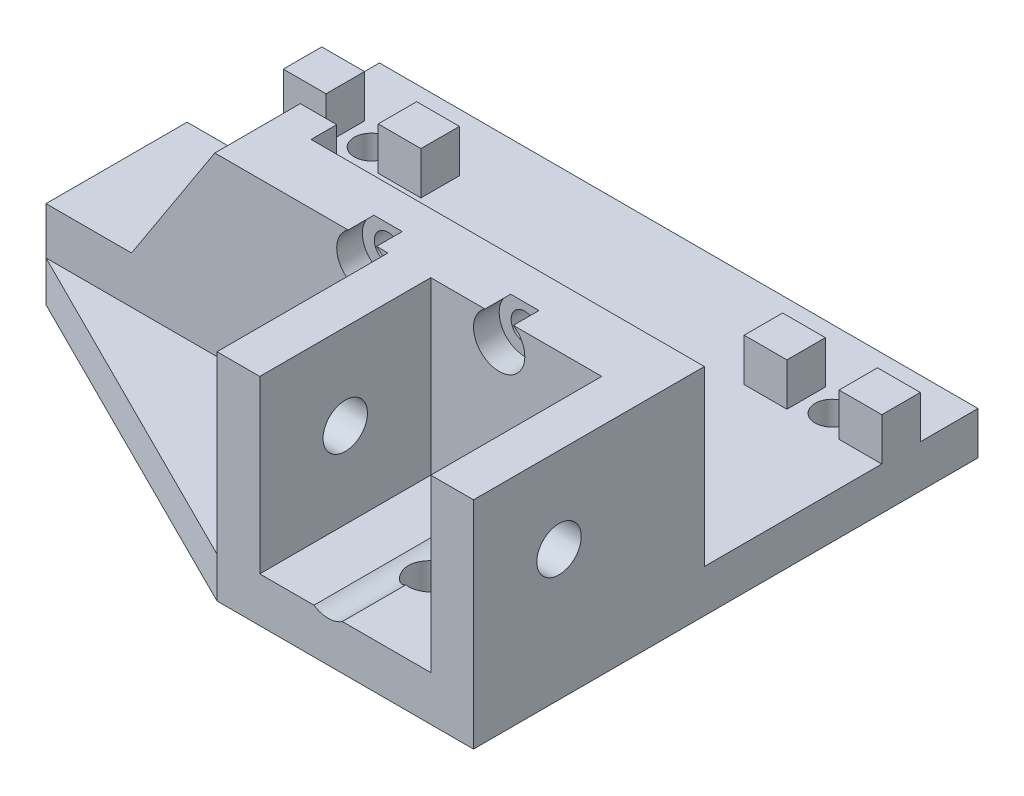
SolidWorks part; units mm, degrees
ref_plane "Front" through (0, 0, 0) normal (0, 0, 1) x (1, 0, 0)
ref_plane "Top" through (0, 0, 0) normal (0, 1, 0) x (1, 0, 0)
ref_plane "Right" through (0, 0, 0) normal (1, 0, 0) x (0, 0, -1)
other "Configuration Table"
sketch "Sketch1" plane through (0, 0, 0) normal (0, 0, 1) x (1, 0, 0)
  line L1 (-20, -10) -> (20, -10)
  line L2 (-20, -10) -> (-20, 10)
  line L3 (-20, 10) -> (20, 10)
  line L4 (20, -10) -> (20, 10)
  line L5 (-20, -10) -> (20, 10) construction
  line L6 (-20, 10) -> (20, -10) construction
  line L7 (-8, -7.5) -> (8, -7.5) construction
  line L8 (-8, -7.5) -> (-8, 7.5) construction
  line L9 (-8, 7.5) -> (8, 7.5) construction
  line L10 (8, -7.5) -> (8, 7.5) construction
  line L11 (-8, -7.5) -> (8, 7.5) construction
  line L12 (-8, 7.5) -> (8, -7.5) construction
  circle A0 centre (-8, 7.5) radius 1.6
  circle A1 centre (8, 7.5) radius 1.6
  circle A2 centre (8, -7.5) radius 1.6
  circle A3 centre (-8, -7.5) radius 1.6
  point P0 (0, 0)
  point P6 (0, 0)
extrude "Boss-Extrude1" add sketch "Sketch1" along normal blind 7
sketch "Sketch2" plane through (20, 0, 0) normal (1, 0, 0) x (0, 0, -1)
  line L0 (0, 0) -> (0, 5) construction
  line L1 (0, -10) -> (0, 10) construction
  line L2 (0, 0) -> (0, -5) construction
  line L3 (0, -5) -> (3, -5) construction
  line L4 (3, -5) -> (3, 5)
  line L5 (3, 5) -> (0, 5) construction
  line L6 (0, -10) -> (9.5, -10)
  line L7 (0, 10) -> (9.5, 10)
  line L8 (9.5, 10) -> (9.5, 5)
  line L9 (9.5, 5) -> (3, 5)
  line L10 (9.5, -10) -> (9.5, -5)
  line L11 (9.5, -5) -> (3, -5)
  line L12 (0, -10) -> (0, -5) construction
  line L13 (0, 5) -> (0, 10) construction
  line L14 (0, -10) -> (-7, -10)
  line L15 (-7, -10) -> (-7, 10)
  line L16 (-7, 10) -> (0, 10)
extrude "Boss-Extrude2" add sketch "Sketch2" along normal blind 5
sketch "Sketch3" plane through (-20, 0, 0) normal (-1, 0, 0) x (0, 0, 1)
  line L0 (7, 10) -> (-9.5, 10)
  line L1 (-9.5, 10) -> (-9.5, 5)
  line L2 (-9.5, 5) -> (-3, 5)
  line L3 (-3, 5) -> (-3, -5)
  line L4 (-3, -5) -> (-9.5, -5)
  line L5 (-9.5, -5) -> (-9.5, -10)
  line L6 (-9.5, -10) -> (7, -10)
  line L7 (7, -10) -> (7, 10)
extrude "Boss-Extrude3" add sketch "Sketch3" along normal blind 5
sketch "Sketch4" plane through (0, -10, 0) normal (0, -1, 0) x (1, 0, 0)
  line L0 (-25, 7) -> (-25, -9.5)
  line L1 (-25, -9.5) -> (-20, -9.5)
  line L2 (-20, -9.5) -> (-20, 0)
  line L3 (-20, 0) -> (20, 0)
  line L4 (20, 0) -> (20, -9.5)
  line L5 (20, -9.5) -> (25, -9.5)
  line L6 (25, -9.5) -> (25, 7)
  line L7 (25, 7) -> (-25, 7)
extrude "Boss-Extrude4" add sketch "Sketch4" along normal blind 0.25
sketch "Sketch5" plane through (0, -10.25, 0) normal (0, -1, 0) x (1, 0, 0)
  line L0 (-20, 0) -> (-20, -29) construction
  line L1 (-25, 7) -> (-25, -29)
  line L2 (25, 7) -> (25, -29)
  line L3 (25, -29) -> (-25, -29)
  line L4 (-25, 7) -> (25, 7)
extrude "Boss-Extrude5" add sketch "Sketch5" along normal blind 5
sketch "Sketch6" plane through (0, 0, 7) normal (0, 0, 1) x (1, 0, 0)
  circle A0 centre (-8, 7.5) radius 3
  circle A1 centre (-8, -7.5) radius 3
  circle A2 centre (8, -7.5) radius 3
  circle A3 centre (8, 7.5) radius 3
extrude "Cut-Extrude1" cut sketch "Sketch6" against normal blind 3
sketch "Sketch7" plane through (-25, 0, 0) normal (-1, 0, 0) x (0, 0, 1)
  line L0 (-3, -5) -> (7, -5)
  line L1 (7, -15.25) -> (7, 10) construction
  line L2 (7, -5) -> (7, -15.25)
  line L3 (7, -15.25) -> (-29, -15.25)
  line L4 (-29, -15.25) -> (-29, -10.25)
  line L5 (-29, -10.25) -> (-9.5, -10.25)
  line L6 (-9.5, -10.25) -> (-9.5, -5)
  line L7 (-9.5, -5) -> (-3, -5)
extrude "Boss-Extrude6" add sketch "Sketch7" along normal blind 20
sketch "Sketch9" plane through (0, 0, 7) normal (0, 0, 1) x (1, 0, 0)
  line L0 (0, 0) -> (20, 0) construction
  line L1 (0, 0) -> (0, 10)
  line L2 (-20, 0) -> (-20, 10) construction
  line L3 (20, 0) -> (20, 10)
  line L4 (-20, 0) -> (-20, -10) construction
  line L5 (20, 0) -> (20, -10)
  line L6 (20, -10) -> (25, -10)
  line L7 (25, 10) -> (25, -15.25) construction
  line L8 (25, -10) -> (25, 10)
  line L9 (25, 10) -> (20, 10)
  line L10 (-20, 10) -> (-25, 10) construction
  line L11 (-25, 10) -> (-25, -10) construction
  line L12 (-25, -10) -> (-20, -10) construction
  line L13 (0, 0) -> (0, -10)
  line L14 (0, 10) -> (-5, 10)
  line L15 (-5, 10) -> (-5, -10)
  line L16 (-5, -10) -> (0, -10)
extrude "Boss-Extrude8" add sketch "Sketch9" along normal blind 20
sketch "Sketch10" plane through (-25, 0, 0) normal (-1, 0, 0) x (0, 0, 1)
  line L0 (0, 0) -> (7, 0) construction
  line L1 (7, 0) -> (7, -5) construction
  line L2 (7, 0) -> (17, 0) construction
  circle A0 centre (17, 0) radius 2.6
extrude "Cut-Extrude2" cut sketch "Sketch10" against normal through all
sketch "Sketch11" plane through (0, 0, 7) normal (0, 0, 1) x (1, 0, 0)
  line L0 (-9.6583, 10) -> (-25, 10) construction
  line L2 (10, -10) -> (10, 10) construction
  line L3 (10, 10) -> (-10, 10) construction
  line L4 (-10, -10) -> (-10, 10) construction
  line L5 (10, -10) -> (-10, 10) construction
  line L6 (10, 10) -> (-10, -10) construction
  line L11 (25, -15.25) -> (25, -10)
  line L12 (25, -10) -> (10, -10)
  line L13 (10, -10) -> (9.6583, -10)
  line L15 (-9.6583, -10) -> (9.6583, -10) construction
  line L17 (6.3417, -10) -> (-5, -10)
  line L18 (-5, -10) -> (-5, -15.25)
  line L19 (25, -15.25) -> (-45, -15.25) construction
  line L20 (-5, -15.25) -> (25, -15.25)
  circle A0 centre (8, -7.5) radius 3 construction
  circle A1 centre (-8, -7.5) radius 3 construction
  circle A2 centre (8, -7.5) radius 3 construction
  spline S0 degree 3 poles (9.6583, -10) (9.1046, -10.3723) (7.8997, -10.6752) (6.7571, -10.2766) (6.3417, -10) knots 0 0 0 0 0.571534 1 1 1 1
  point P0 (0, 0)
extrude "Boss-Extrude9" add sketch "Sketch11" along normal through all
sketch "Sketch12" plane through (0, -15.25, 0) normal (0, -1, 0) x (1, 0, 0)
  line L0 (-5, 17) -> (25, 17) construction
  line L1 (-5, 27) -> (-5, 7) construction
  line L2 (25, -29) -> (25, 27) construction
  circle A0 centre (10, 17) radius 2.6
extrude "Cut-Extrude3" cut sketch "Sketch12" against normal through all
sketch "Sketch13" plane through (0, 0, -9.5) normal (0, 0, -1) x (-1, 0, 0)
  line L1 (20, 10) -> (25, 10)
  line L2 (20, 10) -> (20, 5)
  line L3 (20, 5) -> (25, 5)
  line L4 (25, 10) -> (25, 5)
  line L5 (-20, 5) -> (-25, 5)
  line L6 (-20, 5) -> (-20, 10)
  line L7 (-20, 10) -> (-25, 10)
  line L8 (-25, 5) -> (-25, 10)
extrude "Cut-Extrude4" cut sketch "Sketch13" against normal up to surface (6.5 mm away) up to face at (22.5, 0, -3)
chamfer "Chamfer1" distance 10 angle 57 1 edges at (-25, -5, 2) first distance on face at (-30, -5, -1.8333)
sketch "Sketch14" plane through (0, 0, 0) normal (0, 0, -1) x (-1, 0, 0)
  line L0 (20, 10) -> (21, 10)
  line L1 (25.2589, 10) -> (20, 10) construction
  line L2 (21, 10) -> (21, -10.25)
  line L3 (45, -10.25) -> (20, -10.25) construction
  line L4 (21, -10.25) -> (20, -10.25)
  line L5 (20, -10.25) -> (20, 10)
  line L6 (-20, 10) -> (-21, 10)
  line L7 (-20, 10) -> (-25, 10) construction
  line L8 (-21, 10) -> (-21, -10.25)
  line L9 (45, -10.25) -> (-25, -10.25) construction
  line L10 (-20, -10.25) -> (-25, -10.25) construction
  line L11 (-21, -10.25) -> (-20, -10.25)
  line L12 (-20, -10.25) -> (-20, 10)
extrude "Cut-Extrude5" cut sketch "Sketch14" along normal blind 10
sketch "Sketch16" plane through (0, 0, 0) normal (0, 0, -1) x (-1, 0, 0)
  line L0 (-21, 10) -> (-21, -10.25)
  line L1 (-21, -10.25) -> (-25, -10.25)
  line L2 (-25, -10.25) -> (-25, 10)
  line L3 (-25, 10) -> (-21, 10)
extrude "Cut-Extrude7" cut sketch "Sketch16" along normal blind 10
sketch "Sketch17" plane through (0, -15.25, 0) normal (0, -1, 0) x (1, 0, 0)
  line L0 (-5, 27) -> (-45, 7)
  line L1 (-45, 7) -> (-5, 7)
  line L2 (-5, 7) -> (-5, 27)
extrude "Boss-Extrude10" add sketch "Sketch17" against normal blind 4.75
sketch "Sketch18" plane through (0, 0, -29) normal (0, 0, -1) x (-1, 0, 0)
  line L0 (45, -15.25) -> (-25, -15.25)
  line L1 (-25, -15.25) -> (-25, -10.25)
  line L2 (-25, -10.25) -> (45, -10.25)
  line L3 (45, -10.25) -> (45, -15.25)
extrude "Boss-Extrude11" add sketch "Sketch18" along normal blind 3
sketch "Sketch8" plane through (0, -10.25, 0) normal (0, 1, 0) x (1, 0, 0)
  line L0 (20, 23) -> (25, 23) construction
  line L1 (-45, 18.1812) -> (25, 18.1812) construction
  line L2 (20, 22.25) -> (20, 25.25) construction
  line L3 (20, 20.75) -> (20, 25.25)
  line L5 (20, 20.75) -> (22, 20.75)
  line L8 (20, 23) -> (13.9, 23) construction
  line L9 (13.9, 23) -> (13.9, 20.75)
  line L10 (13.9, 20.75) -> (11.9, 20.75)
  line L15 (-10, 18.1812) -> (-10, 25.1041) construction
  line L16 (-40, 23) -> (-33.9, 23) construction
  line L17 (-40, 23) -> (-45, 23) construction
  line L27 (13.9, 23) -> (13.9, 25.25)
  line L28 (13.9, 25.25) -> (8.9, 25.25)
  line L29 (20, 25.25) -> (25, 25.25)
  line L30 (25, 25.25) -> (25, 20.75)
  line L31 (25, 20.75) -> (22, 20.75)
  line L32 (11.9, 20.75) -> (8.9, 20.75)
  line L33 (8.9, 20.75) -> (8.9, 25.25)
  line L34 (-28.9, 20.75) -> (-28.9, 25.25)
  line L35 (-31.9, 20.75) -> (-28.9, 20.75)
  line L36 (-45, 20.75) -> (-42, 20.75)
  line L37 (-45, 25.25) -> (-45, 20.75)
  line L38 (-40, 25.25) -> (-45, 25.25)
  line L39 (-33.9, 25.25) -> (-28.9, 25.25)
  line L40 (-33.9, 23) -> (-33.9, 25.25)
  line L41 (-33.9, 20.75) -> (-31.9, 20.75)
  line L42 (-33.9, 23) -> (-33.9, 20.75)
  line L43 (-40, 20.75) -> (-42, 20.75)
  line L44 (-40, 20.75) -> (-40, 25.25)
  point P10 (20, 23)
  point P37 (-40, 23)
extrude "Boss-Extrude7" add sketch "Sketch8" along normal blind 5
sketch "Sketch15" plane through (0, -10.25, 0) normal (0, 1, 0) x (1, 0, 0)
  line L0 (20, 23) -> (13.9, 23) construction
  line L2 (20, 25.25) -> (20, 20.75) construction
  line L3 (-33.9, 19.95) -> (-40, 20) construction
  line L4 (13.9, 20.75) -> (13.9, 25.25) construction
  line L5 (13.9, 23) -> (-33.9, 23) construction
  line L6 (-33.9, 25.25) -> (-33.9, 20.75) construction
  line L7 (-33.9, 23) -> (-40, 23) construction
  line L8 (-40, 20.75) -> (-40, 25.25) construction
  circle A0 centre (16.95, 23) radius 2
  circle A1 centre (-36.95, 23) radius 2
extrude "Cut-Extrude6" cut sketch "Sketch15" against normal blind 10
